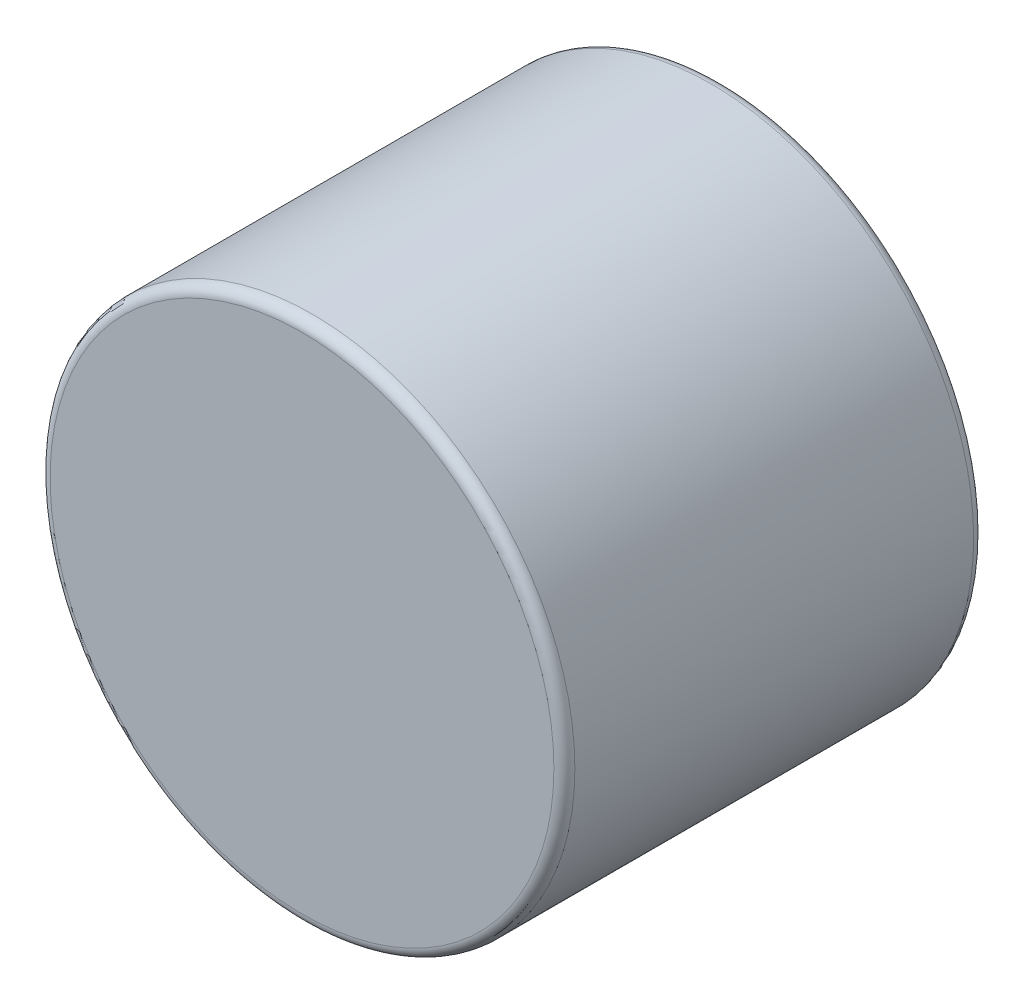
SolidWorks part; units mm, degrees
ref_plane "Front Plane" through (0, 0, 0) normal (0, 0, 1) x (1, 0, 0)
ref_plane "Top Plane" through (0, 0, 0) normal (0, 1, 0) x (1, 0, 0)
ref_plane "Right Plane" through (0, 0, 0) normal (1, 0, 0) x (0, 0, -1)
sketch "Sketch1" plane through (0, 0, 0) normal (0, 0, 1) x (1, 0, 0)
  circle A0 centre (0, 0) radius 3.9688 construction
  dimension "OD" = 7.9375
sketch "Sketch2" plane through (0, 0, 0) normal (1, 0, 0) x (0, 0, -1)
  line L0 (-3.175, 0) -> (3.175, 0) construction
  line L1 (0, 3.9688) -> (0, -3.9688) construction
  line L3 (-3.175, 3.9688) -> (3.175, 3.9688)
  line L4 (-3.175, 3.9688) -> (-3.175, -3.9688)
  line L5 (-3.175, -3.9688) -> (3.175, -3.9688)
  line L6 (3.175, 3.9688) -> (3.175, -3.9688)
  point P4 (0, 0)
  point P12 (0, 3.9688)
  dimension "Thickness" = 6.35
sketch "Sketch3" plane through (0, 0, 0) normal (0, 0, 1) x (1, 0, 0)
  circle A0 centre (0, 0) radius 3.9688 construction
  circle A1 centre (0, 0) radius 3.9688
extrude "Boss-Extrude1" add sketch "Sketch3" along normal up to vertex (3.175 mm away) and the other way up to vertex (3.175 mm away) up to point (0, 3.9688, 3.175) other way up to point (0, 3.9688, -3.175)
fillet "Fillet1" radius 0.1588 2 edges at (3.9688, 0, -3.175) (3.9688, 0, 3.175)
equation "\"Fillet@Fillet1\"=\"Thickness@Sketch2\"*.025"
